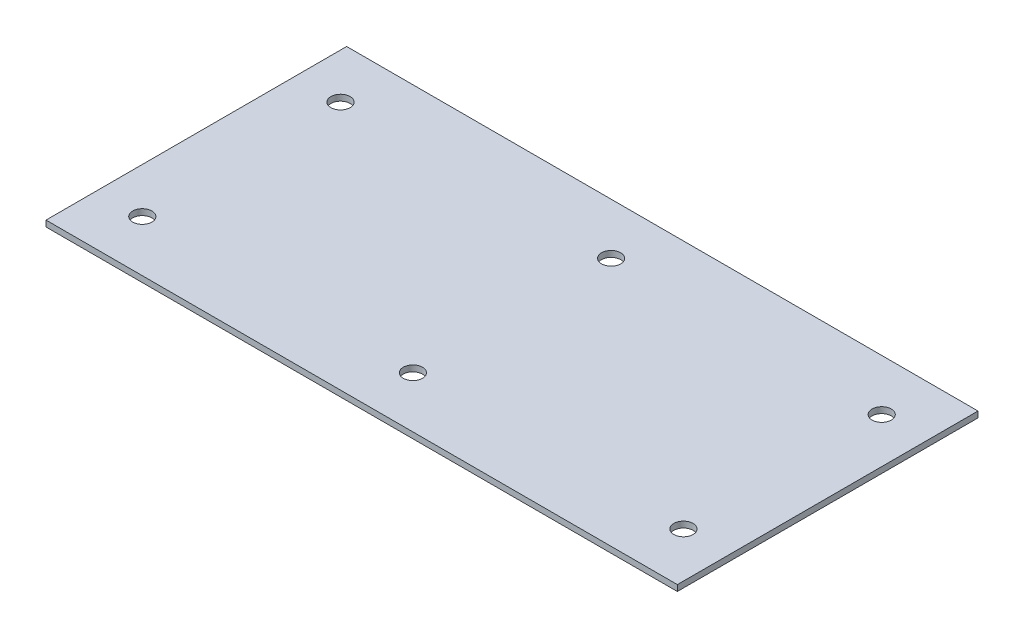
SolidWorks part; units mm, degrees
ref_plane "Спереди" through (0, 0, 0) normal (0, 0, 1) x (1, 0, 0)
ref_plane "Сверху" through (0, 0, 0) normal (0, 1, 0) x (1, 0, 0)
ref_plane "Справа" through (0, 0, 0) normal (1, 0, 0) x (0, 0, -1)
sketch "Эскиз1" plane through (0, 0, 0) normal (0, 1, 0) x (1, 0, 0)
  line L0 (15, 17.0342) -> (195, 17.0342) construction
  line L5 (0, 0) -> (210, 0)
  line L6 (0, 0) -> (0, 100)
  line L7 (0, 100) -> (210, 100)
  line L8 (210, 0) -> (210, 100)
  line L9 (0, 50) -> (210, 50) construction
  circle A0 centre (195, 17.0342) radius 3.2
  circle A1 centre (105, 17.0342) radius 3.2
  circle A2 centre (15, 17.0342) radius 3.2
  circle A3 centre (195, 82.9658) radius 3.2
  circle A4 centre (105, 82.9658) radius 3.2
  circle A5 centre (15, 82.9658) radius 3.2
  dimension "D1" = 210
  dimension "D2" = 100
extrude "Бобышка-Вытянуть1" add sketch "Эскиз1" along normal blind 2
